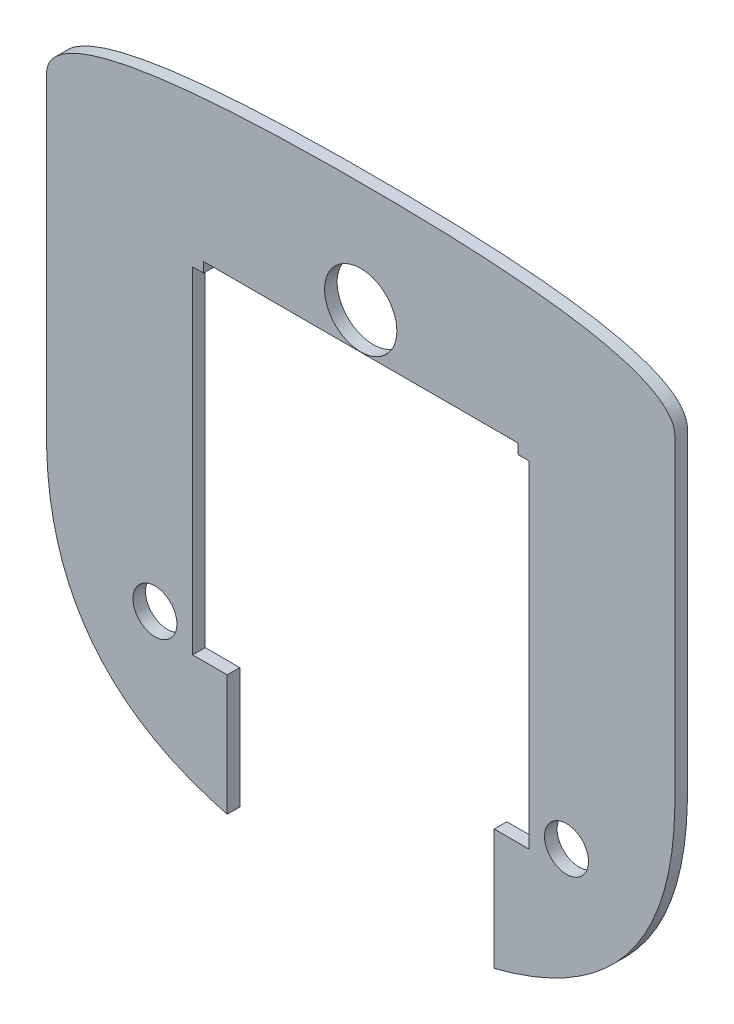
SolidWorks part; units mm, degrees
ref_plane "Front Plane" through (0, 0, 0) normal (0, 0, 1) x (1, 0, 0)
ref_plane "Top Plane" through (0, 0, 0) normal (0, 1, 0) x (1, 0, 0)
ref_plane "Right Plane" through (0, 0, 0) normal (1, 0, 0) x (0, 0, -1)
ref_plane "Plane1" through (0, 0, 804.734) normal (0, 0, 1) x (1, 0, 0)
sketch "Sketch1" plane through (0, 0, 804.734) normal (0, 0, 1) x (1, 0, 0)
  line L0 (0, 70.1122) -> (0, -75.0001) construction
  line L1 (0, 70.1122) -> (0, -36.8878) construction
  line L4 (53.5, -36.8878) -> (53.5, 70.1122) construction
  line L7 (53.5, -36.8878) -> (53.5, 70.1122)
  line L8 (53.5, 70.1122) -> (50, 70.1122)
  line L9 (50, 70.1122) -> (50, 73.2872)
  line L10 (50, 73.2872) -> (-50, 73.2872)
  line L11 (-50, 73.2872) -> (-50, 70.1122)
  line L12 (-50, 70.1122) -> (-50, 73.2872) construction
  line L13 (-50, 70.1122) -> (-53.5, 70.1122)
  line L14 (-53.5, 70.1122) -> (-53.5, -36.8878)
  line L15 (-53.5, -36.8878) -> (-42.5, -36.8878)
  line L16 (42.5, -36.8878) -> (42.5, -75.3262) construction
  line L17 (42.5, -36.8878) -> (42.5, -75.3262)
  line L18 (-42.5, -36.8878) -> (-42.5, -75.3262) construction
  line L19 (-42.5, -36.8878) -> (-42.5, -75.3262)
  line L20 (42.5, -36.8878) -> (53.5, -36.8878)
  circle A0 centre (0, 84.8872) radius 11.5 construction
  circle A1 centre (0, 84.8872) radius 11.5
  circle A2 centre (65.5, -30.8878) radius 7
  circle A3 centre (-65.5, -30.8878) radius 7
  spline S0 degree 3 poles (100, 91.6667) (100, 100.5541) (99.8835, 101.663) (99.344, 103.2464) (98.4974, 104.6847) (97.0622, 106.3843) (94.8888, 108.1258) (91.9976, 109.7782) (88.9551, 111.1271) (85.8262, 112.2552) (82.6425, 113.2169) (79.4227, 114.0479) (76.1777, 114.7739) (72.9147, 115.4129) (69.6383, 115.979) (65.2561, 116.6501) (59.7591, 117.3544) (53.1437, 118.032) (46.5161, 118.5751) (37.6683, 119.1501) (26.5955, 119.6359) (13.2992, 119.9414) (4.4331, 120) (-4.4331, 120) (-13.2992, 119.9414) (-26.5955, 119.6359) (-37.6683, 119.1501) (-46.5161, 118.5751) (-53.1437, 118.032) (-59.7591, 117.3544) (-65.2561, 116.6501) (-69.6383, 115.979) (-72.9147, 115.4129) (-76.1777, 114.7739) (-79.4227, 114.0479) (-82.6425, 113.2169) (-85.8262, 112.2552) (-88.9551, 111.1271) (-91.9976, 109.7782) (-94.8888, 108.1258) (-97.0622, 106.3843) (-98.4974, 104.6847) (-99.344, 103.2464) (-99.8835, 101.663) (-100, 100.5541) (-100, 91.6667) (-100, 75) (-100, 50) (-100, 25) (-100, 8.3333) (-100, -3.0509) (-99.7823, -9.1535) (-98.6814, -18.2496) (-96.6708, -27.1928) (-93.6177, -35.841) (-89.4261, -44.0037) (-84.0794, -51.4648) (-77.6729, -58.0369) (-70.3884, -63.6161) (-62.4486, -68.1997) (-51.2385, -73.0758) (-36.4788, -77.1218) (-18.3084, -79.5568) (-6.1019, -80) (6.1019, -80) (18.3084, -79.5568) (36.4788, -77.1218) (51.2385, -73.0758) (62.4486, -68.1997) (70.3884, -63.6161) (77.6729, -58.0369) (84.0794, -51.4648) (89.4261, -44.0037) (93.6177, -35.841) (96.6708, -27.1928) (98.6814, -18.2496) (99.7823, -9.1535) (100, -3.0509) (100, 8.3333) (100, 25) (100, 50) (100, 75) (100, 91.6667) (100, 100.5541) (99.8835, 101.663) knots -0.070853 -0.035426 0 0 0.002356 0.004712 0.007067 0.009423 0.014135 0.018847 0.023558 0.02827 0.032982 0.037693 0.042405 0.047116 0.051828 0.05654 0.065963 0.075386 0.08481 0.094233 0.11308 0.131926 0.150773 0.150773 0.169619 0.188466 0.207313 0.216736 0.226159 0.235583 0.245006 0.249718 0.254429 0.259141 0.263853 0.268564 0.273276 0.277988 0.282699 0.287411 0.292123 0.294478 0.296834 0.29919 0.301546 0.301546 0.336972 0.372399 0.407825 0.443252 0.443252 0.456222 0.469192 0.482162 0.495132 0.508102 0.521072 0.534042 0.547012 0.559982 0.572952 0.598893 0.624833 0.650773 0.650773 0.676713 0.702653 0.728593 0.741563 0.754533 0.767504 0.780474 0.793444 0.806414 0.819384 0.832354 0.845324 0.858294 0.858294 0.893721 0.929147 0.964574 1 1 1.002356 1.004712 1.007067 only from (-84.3548, -50.7704) to (-84.3548, -50.7704)
  spline S1 degree 3 poles (42.5, -75.3262) (46.3934, -74.3338) (53.1534, -72.2429) (62.4486, -68.1997) (70.3884, -63.6161) (77.6729, -58.0369) (84.0794, -51.4648) (89.4261, -44.0037) (93.6177, -35.841) (96.6708, -27.1928) (98.6814, -18.2496) (99.7823, -9.1535) (100, -3.0509) (100, 25) (100, 58.3333) (100, 91.6667) (100, 100.5541) (99.8835, 101.663) (99.344, 103.2464) (98.4974, 104.6847) (97.0622, 106.3843) (94.8888, 108.1258) (91.9976, 109.7782) (88.9551, 111.1271) (85.8262, 112.2552) (82.6425, 113.2169) (79.4227, 114.0479) (76.1777, 114.7739) (72.9147, 115.4129) (69.6383, 115.979) (65.2561, 116.6501) (59.7591, 117.3544) (53.1437, 118.032) (46.5161, 118.5751) (37.6683, 119.1501) (26.5955, 119.6359) (13.2992, 119.9414) (4.4331, 120) (-4.4331, 120) (-13.2992, 119.9414) (-26.5955, 119.6359) (-37.6683, 119.1501) (-46.5161, 118.5751) (-53.1437, 118.032) (-59.7591, 117.3544) (-65.2561, 116.6501) (-69.6383, 115.979) (-72.9147, 115.4129) (-76.1777, 114.7739) (-79.4227, 114.0479) (-82.6425, 113.2169) (-85.8262, 112.2552) (-88.9551, 111.1271) (-91.9976, 109.7782) (-94.8888, 108.1258) (-97.0622, 106.3843) (-98.4974, 104.6847) (-99.344, 103.2464) (-99.8835, 101.663) (-100, 100.5541) (-100, 91.6667) (-100, 58.3333) (-100, 25) (-100, -3.0509) (-99.7823, -9.1535) (-98.6814, -18.2496) (-96.6708, -27.1928) (-93.6177, -35.841) (-89.4261, -44.0037) (-84.0794, -51.4648) (-77.6729, -58.0369) (-70.3884, -63.6161) (-62.4486, -68.1997) (-53.1534, -72.2429) (-46.3934, -74.3338) (-42.5, -75.3262) knots 0.711515 0.711515 0.711515 0.711515 0.728593 0.741563 0.754533 0.767504 0.780474 0.793444 0.806414 0.819384 0.832354 0.845324 0.858294 0.858294 0.964574 1 1 1.002356 1.004712 1.007067 1.009423 1.014135 1.018847 1.023558 1.02827 1.032982 1.037693 1.042405 1.047116 1.051828 1.05654 1.065963 1.075386 1.08481 1.094233 1.11308 1.131926 1.150773 1.150773 1.169619 1.188466 1.207313 1.216736 1.226159 1.235583 1.245006 1.249718 1.254429 1.259141 1.263853 1.268564 1.273276 1.277988 1.282699 1.287411 1.292123 1.294478 1.296834 1.29919 1.301546 1.301546 1.336972 1.443252 1.443252 1.456222 1.469192 1.482162 1.495132 1.508102 1.521072 1.534042 1.547012 1.559982 1.572952 1.59003 1.59003 1.59003 1.59003
  spline S3 degree 3 poles (95, 99.8195) (95.0001, 100.0314) (94.9996, 100.055) (94.9968, 100.1512) (94.9873, 100.2868) (94.9607, 100.4882) (94.9114, 100.7029) (94.8095, 101.0175) (94.6182, 101.4225) (94.1218, 102.1565) (93.1017, 103.1851) (91.3924, 104.3808) (89.3811, 105.4677) (86.4331, 106.7634) (82.4277, 108.117) (77.3756, 109.4207) (72.1826, 110.4845) (66.9035, 111.3629) (59.7887, 112.3372) (50.7996, 113.256) (39.9344, 114.0219) (29.0231, 114.5337) (18.0827, 114.8459) (7.1254, 114.9956) (-3.8468, 115.0132) (-14.809, 114.9064) (-25.7552, 114.6458) (-36.6762, 114.1987) (-47.5586, 113.516) (-58.3726, 112.5244) (-67.2845, 111.3448) (-74.2835, 110.0817) (-79.4289, 108.929) (-84.3985, 107.5082) (-88.2737, 106.0221) (-91.0194, 104.6027) (-92.8012, 103.4239) (-93.9105, 102.3936) (-94.4905, 101.6319) (-94.7724, 101.1203) (-94.909, 100.7299) (-94.9691, 100.4345) (-94.9923, 100.2478) (-94.9991, 100.0781) (-95.0001, 100.0336) (-94.9999, 99.7867) (-95, 99.5079) (-95, 99.0452) (-95, 98.4725) (-95, 97.553) (-95, 96.4048) (-95, 94.5669) (-95, 92.2698) (-95, 89.5132) (-95, 86.7566) (-95, 84) (-95, 80.3246) (-95, 75.7303) (-95, 68.3794) (-95, 59.1907) (-95, 48.1644) (-95, 37.1379) (-95, 26.1119) (-95.0001, 16.9221) (-94.9998, 9.5736) (-95.0006, 4.9733) (-94.9992, 1.768) (-95.0014, -0.087) (-94.9924, -1.8304) (-94.9419, -4.0429) (-94.7002, -9.3055) (-93.8557, -17.1391) (-91.5082, -27.252) (-87.7561, -36.8073) (-82.4936, -45.5147) (-73.5142, -55.6568) (-59.0824, -65.1162) (-39.001, -71.662) (-17.8221, -74.6961) (3.8057, -75.29) (25.314, -73.9657) (46.2255, -69.8324) (62.357, -63.0842) (73.4863, -55.1462) (80.6286, -47.9144) (86.3428, -39.5126) (90.5405, -30.1799) (93.2911, -20.2056) (94.516, -11.5676) (94.8995, -5.4398) (94.9828, -2.3519) (95.0011, -0.5986) (94.9994, 1.2124) (95.0002, 3.5226) (94.9999, 7.1929) (95.0001, 13.6282) (95, 22.815) (95, 33.842) (95, 44.8682) (95, 54.0568) (95, 61.4077) (95, 66.9209) (95, 72.4341) (95, 77.9473) (95, 82.5416) (95, 86.2171) (95, 88.9736) (95, 91.2708) (95, 93.1085) (95, 94.4868) (95, 95.865) (95, 97.0139) (95, 97.9322) (95, 98.6228) (95, 99.1926) (95, 99.6027) (95, 99.8195) (95.0001, 100.0314) (94.9996, 100.055) knots -0.000977 -0.000488 -0.000244 0 0.000244 0.000488 0.000977 0.001953 0.00293 0.003906 0.005859 0.007812 0.011719 0.015625 0.019531 0.023438 0.03125 0.039062 0.046875 0.054688 0.0625 0.078125 0.09375 0.109375 0.125 0.140625 0.15625 0.171875 0.1875 0.203125 0.21875 0.234375 0.25 0.257812 0.265625 0.273438 0.28125 0.285156 0.289062 0.292969 0.294922 0.296875 0.298828 0.299805 0.300781 0.30127 0.301514 0.301758 0.302246 0.302734 0.303711 0.304688 0.306641 0.308594 0.3125 0.316406 0.320312 0.324219 0.328125 0.335938 0.34375 0.359375 0.375 0.390625 0.40625 0.421875 0.429688 0.4375 0.441406 0.443359 0.445312 0.449219 0.453125 0.46875 0.484375 0.5 0.515625 0.53125 0.5625 0.59375 0.625 0.65625 0.6875 0.71875 0.75 0.765625 0.78125 0.796875 0.8125 0.828125 0.84375 0.851562 0.855469 0.857422 0.859375 0.863281 0.867188 0.875 0.890625 0.90625 0.921875 0.9375 0.945312 0.953125 0.960938 0.96875 0.976562 0.980469 0.984375 0.988281 0.990234 0.992188 0.994141 0.996094 0.99707 0.998047 0.999023 0.999512 0.999756 1 1.000244 1.000488 1.000977 only from (95, 100) to (95, 100) construction
  dimension "D2" = 14
extrude "Boss-Extrude1" add sketch "Sketch1" against normal blind 4
